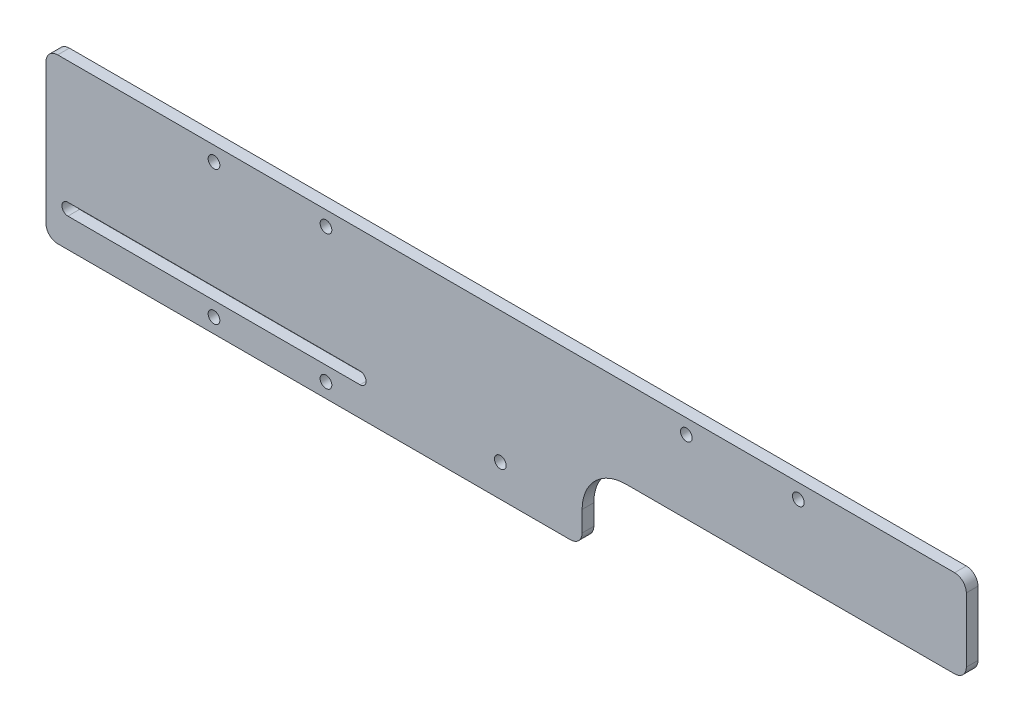
SolidWorks part; units mm, degrees
ref_plane "前视基准面" through (0, 0, 0) normal (0, 0, 1) x (1, 0, 0)
ref_plane "上视基准面" through (0, 0, 0) normal (0, 1, 0) x (1, 0, 0)
ref_plane "右视基准面" through (0, 0, 0) normal (1, 0, 0) x (0, 0, -1)
sketch "草图1" plane through (0, 0, 0) normal (0, 0, 1) x (1, 0, 0)
  line L0 (-150, -16) -> (-50, -16) construction
  line L1 (153.5, -28) -> (-153.5, -28)
  line L2 (157.5, -24) -> (157.5, 24)
  line L3 (153.5, 28) -> (-153.5, 28)
  line L4 (-157.5, -24) -> (-157.5, 24)
  line L5 (157.5, -28) -> (-157.5, 28) construction
  line L6 (157.5, 28) -> (-157.5, -28) construction
  line L7 (-150, -13.95) -> (-50, -13.95)
  line L8 (-150, -18.05) -> (-50, -18.05)
  line L9 (0, 28) -> (0, -28) construction
  arc A0 (157.5, -24) -> (153.5, -28) centre (153.5, -24) cw
  arc A1 (157.5, 24) -> (153.5, 28) centre (153.5, 24) ccw
  arc A2 (-157.5, -24) -> (-153.5, -28) centre (-153.5, -24) ccw
  arc A3 (-157.5, 24) -> (-153.5, 28) centre (-153.5, 24) cw
  arc A4 (-150, -13.95) -> (-150, -18.05) centre (-150, -16) ccw
  arc A5 (-50, -18.05) -> (-50, -13.95) centre (-50, -16) ccw
  circle A7 centre (-100, 23) radius 2
  circle A8 centre (-61.67, 23) radius 2
  circle A9 centre (-100, -23) radius 2
  circle A11 centre (-61.67, -23) radius 2
  circle A12 centre (100, -23) radius 2
  circle A13 centre (61.67, -23) radius 2
  circle A14 centre (61.67, 23) radius 2
  circle A15 centre (100, 23) radius 2
  point P0 (0, 0)
  point P20 (-100, -16)
  dimension "D3" = 4
  dimension "D5" = 7.5
  dimension "D6" = 2.05
  dimension "D7" = 46
  dimension "D8" = 5
  dimension "D9" = 12
  dimension "D10" = 4
  dimension "D11" = 4
  dimension "D12" = 4
  dimension "D13" = 4
  dimension "D14" = 38.33
  dimension "D15" = 38.33
  dimension "D16" = 46
  dimension "D17" = 5
  dimension "D18" = 5
  dimension "D19" = 100
  dimension "D20" = 12
  dimension "D1" = 315
  dimension "D2" = 56
  dimension "D4" = 100
extrude "凸台-拉伸1" add sketch "草图1" along normal blind 4
sketch "草图2" plane through (0, 0, 4) normal (0, 0, 1) x (1, 0, 0)
  line L0 (0, -24) -> (0, -12)
  line L1 (-153.5, -28) -> (153.5, -28) construction
  line L2 (153.5, 28) -> (-153.5, 28) construction
  line L3 (157.5, 2) -> (157.5, -28)
  line L4 (108, -2) -> (10, -2)
  line L5 (112, 28) -> (153.5, 28)
  line L6 (157.5, 24) -> (157.5, 2)
  line L7 (0, -28) -> (157.5, -28)
  line L8 (108, 28) -> (0, 28)
  line L9 (-4, -28) -> (-34.2058, -28)
  line L10 (112, 28) -> (108, 28)
  line L11 (0, -28) -> (-4, -28)
  line L12 (-4, -28) -> (0, -28)
  line L13 (108, -2) -> (153.5, -2)
  line L15 (108, 28) -> (153.5, 28)
  line L16 (157.5, -2) -> (157.5, 24)
  line L17 (0, -28) -> (-4, -28)
  line L18 (153.5, -2) -> (146.4628, -2)
  line L19 (146.4628, -2) -> (153.5, -2)
  arc A0 (-4, -28) -> (0, -24) centre (-4, -24) ccw
  arc A1 (0, -12) -> (10, -2) centre (10, -12) cw
  arc A2 (153.5, -2) -> (157.5, 2) centre (153.5, 2) ccw
  arc A3 (157.5, 24) -> (153.5, 28) centre (153.5, 24) ccw
  point P22 (112, 16)
  arc M8 (153.5, -28) -> (157.5, -24) centre (153.5, -24) ccw
  line M9 (157.5, -24) -> (157.5, 24)
  arc M10 (157.5, 24) -> (153.5, 28) centre (153.5, 24) ccw
  line M11 (153.5, 28) -> (-153.5, 28)
  line M15 (-153.5, -28) -> (153.5, -28)
  circle M25 centre (100, -23) radius 2
  circle M26 centre (61.67, -23) radius 2
  dimension "D3" = 4
  dimension "D2" = 10
  dimension "D4" = 4
  dimension "D1" = 30
extrude "切除-拉伸1" cut sketch "草图2" against normal blind 4 contours L4 A1 L0 A0 M15 M8 M9 M10 M11 M25 M26 | L7 L6 M8 | L6 L5 M10 | M25 | M26 region at (79.0748, -14.9956, 4) region at (156.6065, -27.1065, 4) region at (100, -23, 4) region at (61.67, -23, 4)
sketch "草图3" plane through (0, 0, 4) normal (0, 0, 1) x (1, 0, 0)
  line L0 (153.5, 28) -> (-153.5, 28) construction
  line L1 (-4, -28) -> (22, -28)
  line L2 (-4, -28) -> (-4, 28)
  line L3 (-4, 28) -> (26, 28)
  line L4 (26, -24) -> (26, 24)
  line L5 (30, 28) -> (43.0464, 28)
  line L6 (30, 28) -> (26, 28)
  arc A0 (30, 28) -> (26, 24) centre (30, 24) ccw
  arc A1 (26, -24) -> (22, -28) centre (22, -24) cw
  line M17 (153.5, 28) -> (-153.5, 28)
  arc M22 (-4, -28) -> (0, -24) centre (-4, -24) ccw
  line M23 (0, -24) -> (0, -12)
  arc M24 (0, -12) -> (10, -2) centre (10, -12) cw
  line M25 (10, -2) -> (153.5, -2)
  dimension "D2" = 4
  dimension "D1" = 30
extrude "凸台-拉伸2" add sketch "草图3" against normal blind 4 contours A0 L2 L4 M17 M22 M23 M24 M25 | A1 L4 L1 M25 M24 M23 M22 region at (13.2166, -15.353, 4) region at (9.5912, 9.9812, 4)
sketch "草图17" plane through (0, 0, 4) normal (0, 0, 1) x (1, 0, 0)
  line L0 (26, -8.7425) -> (26, -17)
  line L1 (26, -24) -> (26, -2) construction
  line L2 (41, -2) -> (54.4512, -2)
  line L3 (26, -2) -> (153.5, -2) construction
  line L4 (41, -2) -> (26, -2)
  line L5 (26, -2) -> (26, -17)
  arc A0 (41, -2) -> (26, -17) centre (41, -17) ccw
  point P10 (26, -2)
  line M8 (26, -24) -> (26, -2)
  line M9 (26, -2) -> (153.5, -2)
  dimension "D1" = 15
extrude "凸台-拉伸3" add sketch "草图17" against normal blind 4 contours A0 M9 M8 region at (29.3505, -5.3505, 4)
sketch "草图18" plane through (0, 0, 4) normal (0, 0, 1) x (1, 0, 0)
  circle A0 centre (-2, -17) radius 2
extrude "切除-拉伸2" cut sketch "草图18" against normal through all
